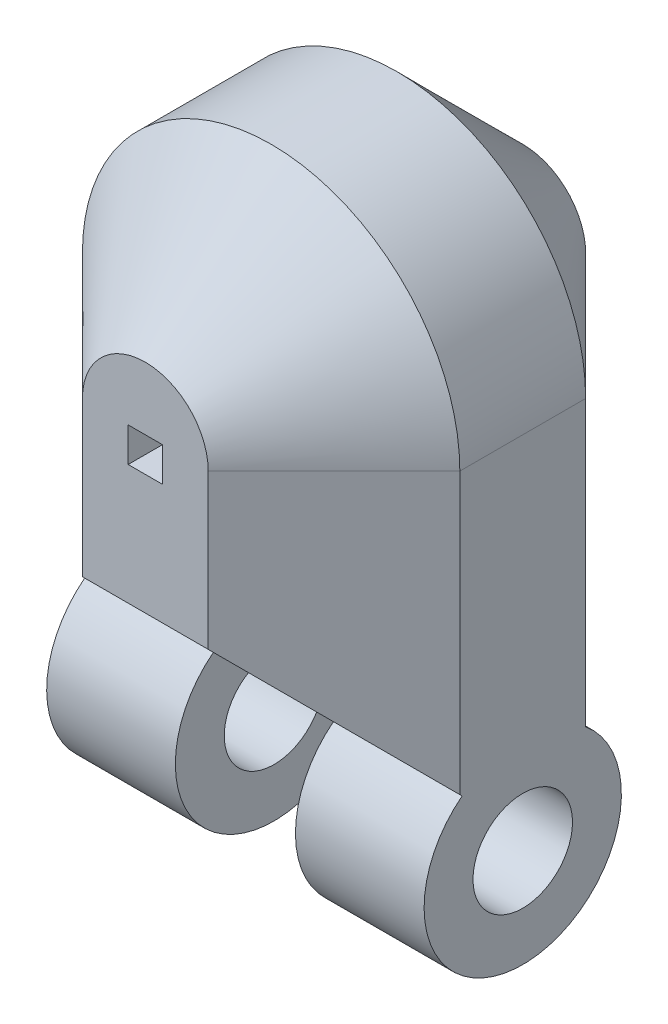
SolidWorks part; units mm, degrees
ref_plane "Front Plane" through (0, 0, 0) normal (0, 0, 1) x (1, 0, 0)
ref_plane "Top Plane" through (0, 0, 0) normal (0, 1, 0) x (1, 0, 0)
ref_plane "Right Plane" through (0, 0, 0) normal (1, 0, 0) x (0, 0, -1)
sketch "Sketch1" plane through (0, 0, 0) normal (0, 1, 0) x (1, 0, 0)
  line L0 (-1.8333, -5.5) -> (1.8333, -5.5)
  line L1 (1.8333, -5.5) -> (5.5, -1.8333)
  line L2 (5.5, -1.8333) -> (5.5, 1.8333)
  line L3 (5.5, 1.8333) -> (1.8333, 5.5)
  line L4 (1.8333, 5.5) -> (-1.8333, 5.5)
  line L5 (-1.8333, 5.5) -> (-5.5, 1.8333)
  line L6 (-5.5, 1.8333) -> (-5.5, -1.8333)
  line L7 (-5.5, -1.8333) -> (-1.8333, -5.5)
  point P16 (5.5, 0)
  point P19 (0, -5.5)
  dimension "D1" = 135
  dimension "D2" = 11
  dimension "D3" = 11
  dimension "D4" = 3.6667
extrude "Boss-Extrude1" add sketch "Sketch1" along normal blind 10
sketch "Sketch2" plane through (0, 0, 0) normal (1, 0, 0) x (0, 0, -1)
  line L3 (-5.5, 10) -> (-5.5, 0) construction
  line L5 (0, 0) -> (-5.5, 0)
  line L6 (-1.8333, 0) -> (1.8333, 0) construction
  line L7 (-5.5, 0) -> (-5.5, 5.5)
  line L8 (-5.5, 5.5) -> (0, 0)
  dimension "D2" = 45
extrude "Cut-Extrude1" cut sketch "Sketch2" against normal through all both and the other way through all contours L8 L5 L7
sketch "Sketch3" plane through (0, 0, 0) normal (0, 1, 0) x (1, 0, 0)
  line L0 (0, -4.5) -> (-0.5, -4)
  line L1 (-0.5, -4) -> (-0.5, -3.5)
  line L2 (-0.5, -3.5) -> (0.5, -3.5)
  line L3 (0.5, -3.5) -> (0.5, -4)
  line L4 (0.5, -4) -> (0, -4.5)
  line L6 (0.5, 4.5) -> (0.5, 4)
  line L7 (-0.5, 4.5) -> (0.5, 4.5)
  line L8 (-0.5, 4) -> (-0.5, 4.5)
  line L9 (0, 3.5) -> (-0.5, 4)
  line L10 (0.5, 4) -> (0, 3.5)
  line L11 (1.8333, 5.5) -> (-1.8333, 5.5) construction
  line L12 (-1.8333, -5.5) -> (1.8333, -5.5) construction
  point P6 (0, -3.5)
  point P13 (0, -5.5)
  dimension "D1" = 1
  dimension "D2" = 0.5
  dimension "D3" = 0.5
  dimension "D4" = 0.5
  dimension "D5" = 1
  dimension "D6" = 2
  dimension "D7" = 1
extrude "Cut-Extrude2" cut sketch "Sketch3" along normal blind 10
sketch "Sketch6" plane through (0, 0, 0) normal (1, 0, 0) x (0, 0, -1)
  circle A0 centre (0, -0.5) radius 3.25
  dimension "D2" = 6.5
  dimension "D1" = 0.5
extrude "Cut-Extrude4" cut sketch "Sketch6" against normal mid plane 3.5
sketch "Sketch7" plane through (-1.75, 0, 0) normal (1, 0, 0) x (0, 0, -1)
  circle A0 centre (0, -0.5) radius 2.875
  dimension "D2" = 5.75
  dimension "D1" = 0.5
extrude "Boss-Extrude3" add sketch "Sketch7" against normal up to surface (3.75 mm away) up to face at (-5.5, 4.3667, 0)
sketch "Sketch8" plane through (1.75, 0, 0) normal (-1, 0, 0) x (0, 0, 1)
  circle A0 centre (0, -0.5) radius 2.875
  dimension "D2" = 5.75
  dimension "D1" = 0.5
extrude "Boss-Extrude4" add sketch "Sketch8" against normal up to surface (3.75 mm away) up to face at (5.5, 4.3667, 0)
sketch "Sketch11" plane through (5.5, 0, 0) normal (1, 0, 0) x (0, 0, -1)
  circle A0 centre (0, -0.5) radius 1.45
  dimension "D1" = 2.9
extrude "Cut-Extrude6" cut sketch "Sketch11" against normal through all both and the other way through all
sketch "Sketch12" plane through (0, 10, 0) normal (0, 1, 0) x (1, 0, 0)
  line L0 (0, 5.5) -> (-1.8333, 5.5)
  line L1 (1.8333, 5.5) -> (-1.8333, 5.5) construction
  line L2 (-1.8333, 5.5) -> (-5.5, 1.8333)
  line L3 (-5.5, 1.8333) -> (-5.5, -1.8333)
  line L4 (-5.5, -1.8333) -> (-1.8333, -5.5)
  line L5 (-1.8333, -5.5) -> (0, -5.5)
  line L6 (-1.8333, -5.5) -> (1.8333, -5.5) construction
  line L7 (0, -5.5) -> (0, 5.5)
revolve "Revolve1" add sketch "Sketch12" angle 180 about L7
sketch "Sketch13" plane through (0, 0, 3.5) normal (0, 0, 1) x (1, 0, 0)
  line L1 (0.5, 10) -> (-0.5, 10)
  line L2 (0.5, 10) -> (0.5, 9)
  line L3 (0.5, 9) -> (-0.5, 9)
  line L4 (-0.5, 10) -> (-0.5, 9)
  line L5 (0.5, 10) -> (-0.5, 10) construction
  point P4 (0, 9)
  dimension "D1" = 1
  dimension "D2" = 1
extrude "Cut-Extrude7" cut sketch "Sketch13" along normal through all
sketch "Sketch14" plane through (0, 0, -4.5) normal (0, 0, 1) x (1, 0, 0)
  line L1 (0.5, 9) -> (-0.5, 9)
  line L2 (0.5, 9) -> (0.5, 10)
  line L3 (0.5, 10) -> (-0.5, 10)
  line L4 (-0.5, 9) -> (-0.5, 10)
  line L5 (0.5, 10) -> (-0.5, 10) construction
  point P4 (0, 9)
  dimension "D1" = 1
  dimension "D2" = 1
extrude "Cut-Extrude8" cut sketch "Sketch14" against normal through all
